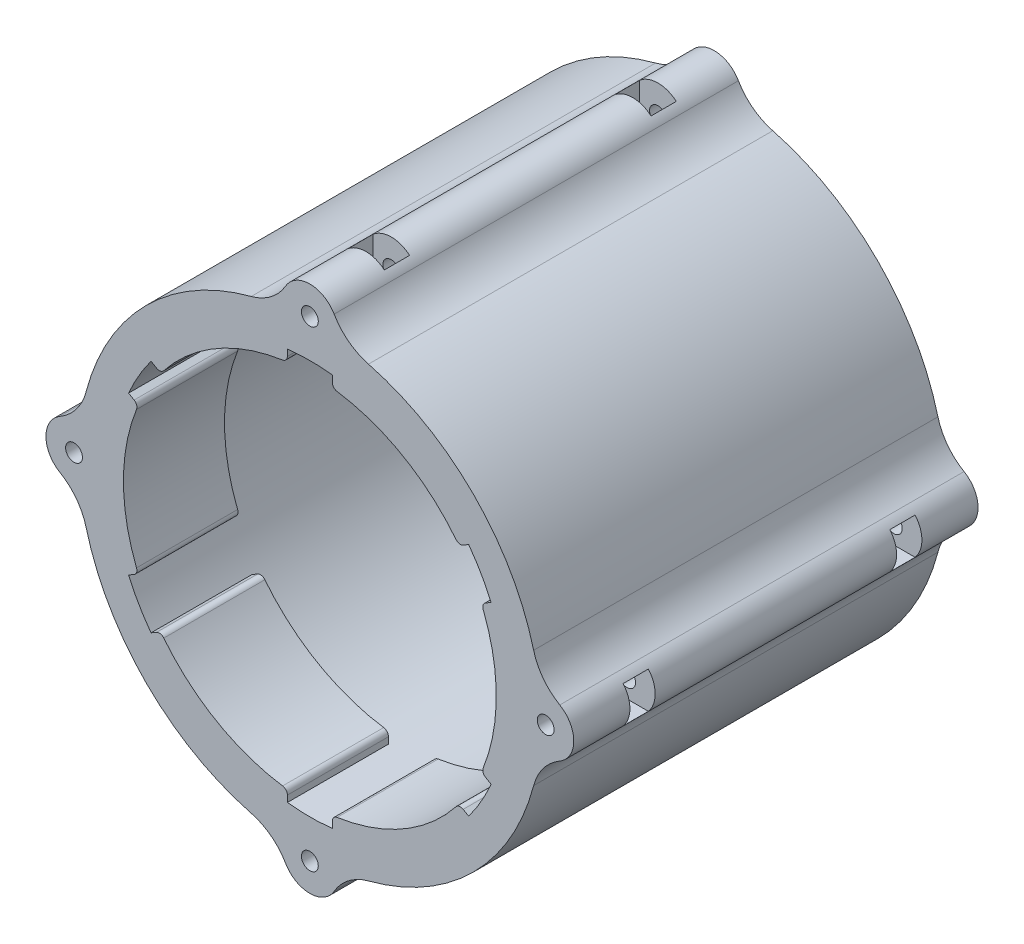
SolidWorks part; units mm, degrees
ref_plane "Ön Düzlem" through (0, 0, 0) normal (0, 0, 1) x (1, 0, 0)
ref_plane "Üst Düzlem" through (0, 0, 0) normal (0, 1, 0) x (1, 0, 0)
ref_plane "Sağ Düzlem" through (0, 0, 0) normal (1, 0, 0) x (0, 0, -1)
sketch "Çizim1" plane through (0, 0, 0) normal (0, 0, 1) x (1, 0, 0)
  circle A0 centre (0, 0) radius 35.2
  arc A1 (-39.8554, -10.4397) -> (-10.4397, -39.8554) centre (0, 0) ccw
  circle A6 centre (-42, 0) radius 1.5
  arc A7 (-44.5097, 4.3245) -> (-44.5097, -4.3245) centre (-42, 0) ccw
  circle A8 centre (0, 0) radius 41.2 construction
  arc A9 (-39.8554, -10.4397) -> (-44.5097, -4.3245) centre (-49.529, -12.9736) ccw
  arc A10 (-39.8554, 10.4397) -> (-44.5097, 4.3245) centre (-49.529, 12.9736) cw
  circle A11 centre (0, 42) radius 1.5
  arc A12 (4.3245, 44.5097) -> (-4.3245, 44.5097) centre (0, 42) ccw
  arc A13 (-10.4397, 39.8554) -> (-4.3245, 44.5097) centre (-12.9736, 49.529) ccw
  arc A14 (10.4397, 39.8554) -> (4.3245, 44.5097) centre (12.9736, 49.529) cw
  circle A15 centre (42, 0) radius 1.5
  arc A16 (44.5097, -4.3245) -> (44.5097, 4.3245) centre (42, 0) ccw
  arc A17 (39.8554, 10.4397) -> (44.5097, 4.3245) centre (49.529, 12.9736) ccw
  arc A18 (39.8554, -10.4397) -> (44.5097, -4.3245) centre (49.529, -12.9736) cw
  circle A19 centre (0, -42) radius 1.5
  arc A20 (-4.3245, -44.5097) -> (4.3245, -44.5097) centre (0, -42) ccw
  arc A21 (10.4397, -39.8554) -> (4.3245, -44.5097) centre (12.9736, -49.529) ccw
  arc A22 (-10.4397, -39.8554) -> (-4.3245, -44.5097) centre (-12.9736, -49.529) cw
  arc A23 (-10.4397, 39.8554) -> (-39.8554, 10.4397) centre (0, 0) ccw
  arc A24 (39.8554, 10.4397) -> (10.4397, 39.8554) centre (0, 0) ccw
  arc A25 (10.4397, -39.8554) -> (39.8554, -10.4397) centre (0, 0) ccw
  point P16 (0, 0)
  point P41 (0, 0)
  dimension "D1" = 70.4
  dimension "D3" = 5
  dimension "D4" = 3
  dimension "D5" = 42
  dimension "D6" = 10
  dimension "D2" = 6
  dimension "D7" = 4
extrude "Yükseklik-Ekstrüzyon1" add sketch "Çizim1" along normal blind 72
sketch "Çizim2" plane through (0, 0, 72) normal (0, 0, 1) x (1, 0, 0)
  line L0 (-4, 34.972) -> (-4, 32.9582)
  line L1 (4, 34.972) -> (4, 32.9582)
  line L2 (28.2866, 20.9501) -> (26.5426, 19.9432)
  line L3 (32.2866, 14.0219) -> (30.5426, 13.015)
  line L4 (32.2866, -14.0219) -> (30.5426, -13.015)
  line L5 (28.2866, -20.9501) -> (26.5426, -19.9432)
  line L6 (4, -34.972) -> (4, -32.9582)
  line L7 (-4, -34.972) -> (-4, -32.9582)
  line L8 (-28.2866, -20.9501) -> (-26.5426, -19.9432)
  line L9 (-32.2866, -14.0219) -> (-30.5426, -13.015)
  line L10 (-32.2866, 14.0219) -> (-30.5426, 13.015)
  line L11 (-28.2866, 20.9501) -> (-26.5426, 19.9432)
  arc A3 (-4, 34.972) -> (-28.2866, 20.9501) centre (0, 0) ccw
  arc A29 (-30.5426, 13.015) -> (-30.5426, -13.015) centre (0, 0) ccw
  arc A30 (-4, 32.9582) -> (-26.5426, 19.9432) centre (0, 0) ccw
  arc A31 (28.2866, 20.9501) -> (4, 34.972) centre (0, 0) ccw
  arc A34 (32.2866, -14.0219) -> (32.2866, 14.0219) centre (0, 0) ccw
  arc A36 (4, -34.972) -> (28.2866, -20.9501) centre (0, 0) ccw
  arc A38 (-28.2866, -20.9501) -> (-4, -34.972) centre (0, 0) ccw
  arc A40 (-32.2866, 14.0219) -> (-32.2866, -14.0219) centre (0, 0) ccw
  arc A41 (26.5426, 19.9432) -> (4, 32.9582) centre (0, 0) ccw
  arc A42 (30.5426, -13.015) -> (30.5426, 13.015) centre (0, 0) ccw
  arc A43 (4, -32.9582) -> (26.5426, -19.9432) centre (0, 0) ccw
  arc A44 (-26.5426, -19.9432) -> (-4, -32.9582) centre (0, 0) ccw
  point P2 (0, 0)
  point P3 (0, 0)
  point P55 (0, 0)
  dimension "D2" = 2
  dimension "D1" = 70.4
  dimension "D3" = 4
  dimension "D5" = 4
  dimension "D8" = 6
extrude "Yükseklik-Ekstrüzyon2" add sketch "Çizim2" against normal blind 18
ref_plane "Düzlem1" through (0, 0, 10) normal (0, 0, -1) x (-1, 0, 0)
sketch "Çizim3" plane through (0, 0, 10) normal (0, 0, -1) x (-1, 0, 0)
  line L0 (-3.262, -42) -> (-3.262, -48)
  line L1 (3.262, -42) -> (1.631, -39.175)
  line L2 (1.631, -39.175) -> (-1.631, -39.175)
  line L3 (-1.631, -39.175) -> (-3.262, -42)
  line L7 (3.262, -42) -> (3.262, -48)
  line L8 (3.262, -48) -> (-3.262, -48)
  line L9 (-2.4465, -43.4125) -> (-1.631, -44.825) [skipped]
  line L10 (0, -44.825) -> (1.631, -44.825) [skipped]
  line L11 (2.4465, -43.4125) -> (3.262, -42) [skipped]
  circle A0 centre (0, -42) radius 2.825 construction
  dimension "D1" = 3.262
  dimension "D2" = 6
  dimension "D3" = 6
  dimension "D4" = 3.262
  dimension "D5" = 3.262
extrude "Kes-Ekstrüzyon1" cut sketch "Çizim3" against normal blind 4.5
pattern_circular "Dairesel Kaplama1" count 4 every 90 about axis through (0, 0, 0) along (0, 0, 1) of "Kes-Ekstrüzyon1"
ref_plane "Düzlem2" through (0, 0, 36) normal (0, 0, -1) x (-1, 0, 0)
mirror "Aynalama1" about plane through (0, 0, 36) normal (0, 0, -1) of "Dairesel Kaplama1"
fillet "Radyus1" radius 1 12 edges at (4, 32.9582, 63) (-4, 32.9582, 63) (26.5426, -19.9432, 63) (30.5426, -13.015, 63) (-4, -32.9582, 63) (4, -32.9582, 63) (-26.5426, -19.9432, 63) (-30.5426, -13.015, 63) (-30.5426, 13.015, 63) (-26.5426, 19.9432, 63) (30.5426, 13.015, 63) (26.5426, 19.9432, 63)
